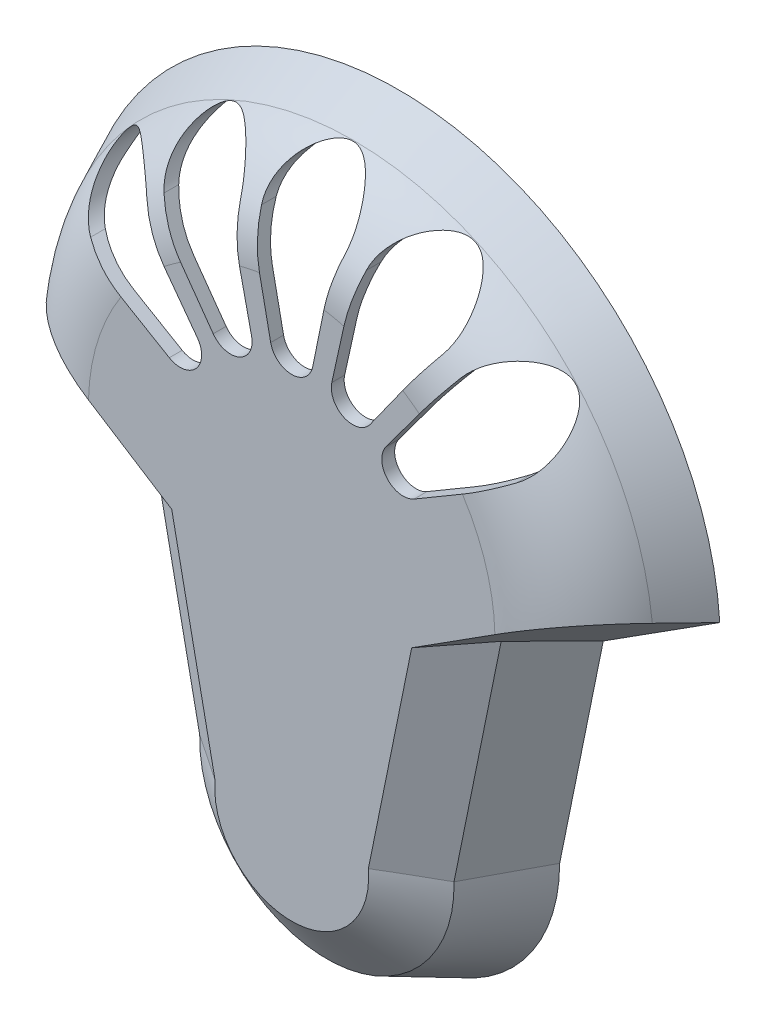
SolidWorks part; units mm, degrees
ref_plane "Front Plane" through (0, 0, 0) normal (0, 0, 1) x (1, 0, 0)
ref_plane "Top Plane" through (0, 0, 0) normal (0, 1, 0) x (1, 0, 0)
ref_plane "Right Plane" through (0, 0, 0) normal (1, 0, 0) x (0, 0, -1)
sketch "Sketch1" plane through (0, 0, 0) normal (0, 0, 1) x (1, 0, 0)
  line L0 (0, 0) -> (0, 92.906) construction
  line L1 (-24.2177, 25.4) -> (-19.05, 0)
  line L2 (-24.2177, 25.4) -> (-38.0215, 34.194)
  line L3 (24.2177, 25.4) -> (38.0215, 34.194)
  line L4 (24.2177, 25.4) -> (19.05, 0)
  arc A0 (19.05, 0) -> (-19.05, 0) centre (0, 0) cw
  arc A1 (-38.0215, 34.194) -> (38.0215, 34.194) centre (0, 31.75) cw
  point P9 (0, 31.75)
  point P10 (0, 0)
  point P12 (0, 0)
  point P13 (0, 0)
  point P14 (0, 0)
  point P15 (0, 0)
  point P16 (0, 0)
  point P17 (0, -8.097)
  point P18 (0, -0.7521)
  point P19 (27.3176, 25.4)
  dimension "D3" = 19.05
  dimension "D6" = 38.1
  dimension "D4" = 23
  dimension "D1" = 31.75
  dimension "D2" = 25.4
  dimension "D5" = 115
extrude "Boss-Extrude1" add sketch "Sketch1" along normal blind 12.7 draft 25
fillet "Fillet1" radius 12.7 1 edges at (0, 63.9279, 12.7)
chamfer "Chamfer1" distance 4.5974 angle 30 3 edges at (-16.0162, 14.7927, 12.7) (16.0162, 14.7927, 12.7) (0, -13.1279, 12.7) first distance on face at (-18.0834, 13.814, 7.9375) first distance on face at (18.0834, 13.814, 7.9375) first distance on face at (0, -7.7738, 9.525)
shell "Shell2" thickness 1.524 removed face at (0, 22.6323, 0)
sketch "Sketch2" plane through (0, 0, 12.7) normal (0, 0, 1) x (1, 0, 0)
  line L0 (0, 31.75) -> (0, 79.9358) construction
  line L1 (-4.9774, 61.214) -> (-2.4887, 49.022)
  line L2 (4.9774, 61.214) -> (2.4887, 49.022)
  line L3 (7.437, 60.6912) -> (4.7516, 48.541)
  line L4 (16.5311, 56.6422) -> (9.2987, 46.5165)
  line L5 (18.5655, 55.1642) -> (11.1703, 45.1567)
  line L6 (25.2265, 47.7664) -> (14.5009, 41.4578)
  line L7 (0, 31.75) -> (2.4887, 49.022) construction
  line L8 (0, 31.75) -> (9.2987, 46.5165) construction
  arc A0 (2.4887, 49.022) -> (-2.4887, 49.022) centre (0, 49.53) cw
  arc A1 (4.9774, 61.214) -> (-4.9774, 61.214) centre (0, 62.23) ccw
  arc A2 (16.5311, 56.6422) -> (7.437, 60.6912) centre (12.3973, 59.5949) ccw
  arc A3 (9.2987, 46.5165) -> (4.7516, 48.541) centre (7.2318, 47.9928) cw
  arc A4 (25.2265, 47.7664) -> (18.5655, 55.1642) centre (22.6511, 52.1451) ccw
  arc A5 (14.5009, 41.4578) -> (11.1703, 45.1567) centre (13.2131, 43.6471) cw
  dimension "D2" = 5.08
  dimension "D3" = 2.54
  dimension "D1" = 12.7
  dimension "D4" = 17.78
  dimension "D6" = 24
  dimension "D7" = 17.4504
  dimension "D5" = 3
extrude "Cut-Extrude1" cut sketch "Sketch2" against normal through all
mirror "Mirror1" about plane through (0, 0, 0) normal (1, 0, 0) of "Cut-Extrude1"
